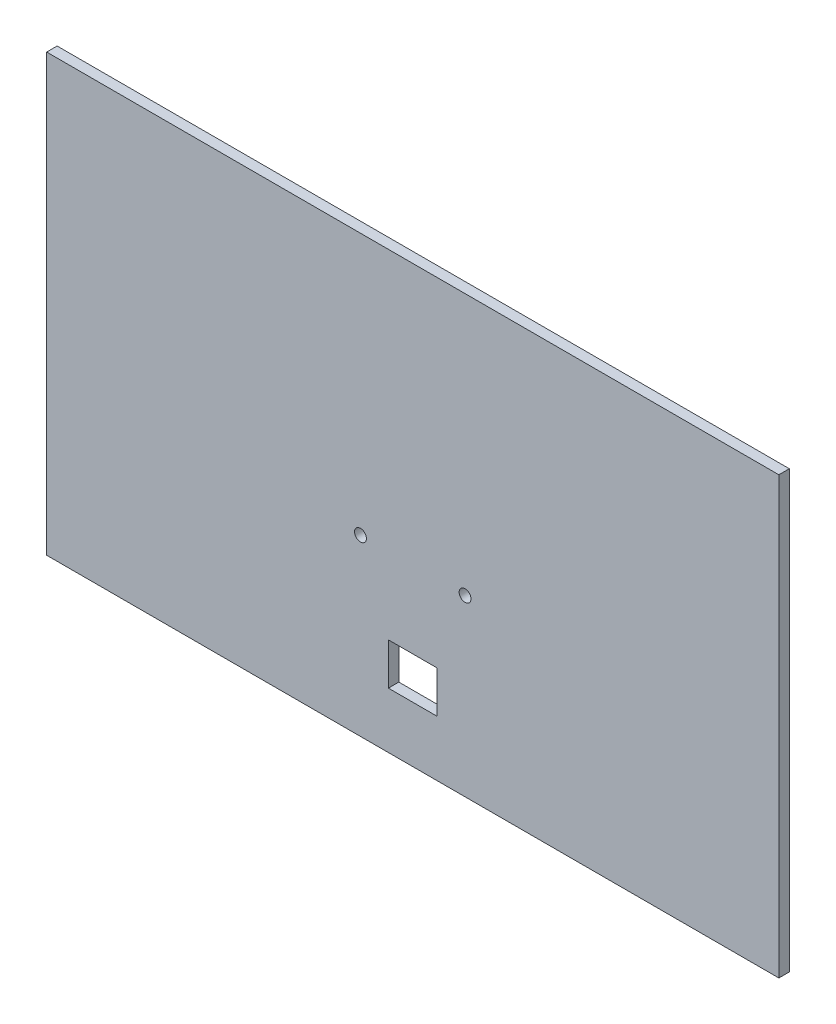
SolidWorks part; units mm, degrees
ref_plane "Front Plane" through (0, 0, 0) normal (0, 0, 1) x (1, 0, 0)
ref_plane "Top Plane" through (0, 0, 0) normal (0, 1, 0) x (1, 0, 0)
ref_plane "Right Plane" through (0, 0, 0) normal (1, 0, 0) x (0, 0, -1)
sketch "SK_Plate" plane through (0, 0, 0) normal (0, 0, 1) x (1, 0, 0)
  line L1 (-105, 0) -> (105, 0)
  line L2 (-105, 0) -> (-105, 125)
  line L3 (-105, 125) -> (105, 125)
  line L4 (105, 0) -> (105, 125)
  dimension "D1" = 210
  dimension "D2" = 125
  dimension "D3" = 105
extrude "EX_Plate" add sketch "SK_Plate" along normal blind 3
sketch "SK_WedgeScrews" plane through (0, 0, 0) normal (0, 0, 1) x (1, 0, 0)
  circle A0 centre (15, 50) radius 1.7
  circle A1 centre (-15, 50) radius 1.7
  dimension "D3" = 3.4
  dimension "D6" = 3.4
  dimension "D1" = 15
  dimension "D2" = 50
  dimension "D4" = 15
  dimension "D5" = 50
extrude "CUT_WedgeScrews" cut sketch "SK_WedgeScrews" along normal blind 3
sketch "SK_USB_Slot" plane through (0, 0, 0) normal (0, 0, 1) x (1, 0, 0)
  line L1 (-7, 16) -> (7, 16)
  line L2 (-7, 16) -> (-7, 28)
  line L3 (-7, 28) -> (7, 28)
  line L4 (7, 16) -> (7, 28)
  dimension "D1" = 14
  dimension "D2" = 12
  dimension "D3" = 7
  dimension "D4" = 16
extrude "CUT_USB_Slot" cut sketch "SK_USB_Slot" along normal blind 3
ref_axis "AX_X" through (0, 0, -0.15) along (0, 0, 1)
ref_axis "AX_Y" through (115.5, 0, 0) along (-1, 0, 0)
ref_axis "AX_Z" through (0, 131.25, 0) along (0, -1, 0)
ref_plane "PL_Zp50" through (0, 50, 0) normal (0, 1, 0) x (1, 0, 0)
sketch "SK_F_IF_Wedge" plane through (0, 50, 0) normal (0, 1, 0) x (1, 0, 0)
  point P0 (0, -3)
  dimension "D1" = 3
